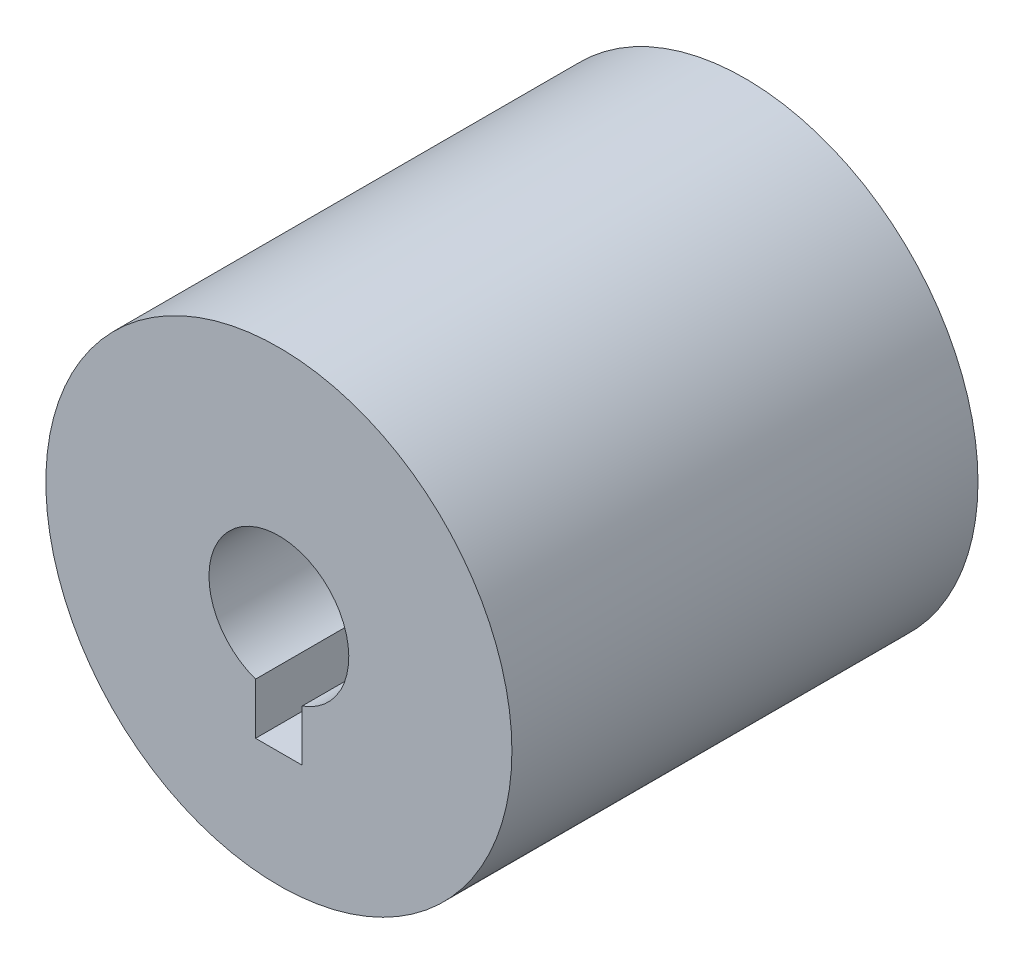
SolidWorks part; units mm, degrees
ref_plane "Front Plane" through (0, 0, 0) normal (0, 0, 1) x (1, 0, 0)
ref_plane "Top Plane" through (0, 0, 0) normal (0, 1, 0) x (1, 0, 0)
ref_plane "Right Plane" through (0, 0, 0) normal (1, 0, 0) x (0, 0, -1)
sketch "Sketch1" plane through (0, 0, 0) normal (0, 0, 1) x (1, 0, 0)
  circle A0 centre (0, 0) radius 5
  dimension "D1" = 10
extrude "Boss-Extrude1" add sketch "Sketch1" along normal blind 10
sketch "Sketch2" plane through (0, 0, 0) normal (0, 0, -1) x (-1, 0, 0)
  line L6 (-0.5, -1.4142) -> (-0.5, -2.5142)
  line L7 (-0.5, -2.5142) -> (0.5, -2.5142)
  line L8 (0.5, -1.4142) -> (0.5, -2.5142)
  arc A1 (0.5, -1.4142) -> (-0.5, -1.4142) centre (0, 0) ccw
  point P3 (0, -1.5)
  dimension "D1" = 3
  dimension "D2" = 1.1
  dimension "D3" = 1
extrude "Cut-Extrude1" cut sketch "Sketch2" against normal blind 10
sketch "Sketch3" plane through (0, 0, 10) normal (0, 0, 1) x (1, 0, 0)
  circle A1 centre (0, 0) radius 11
  dimension "D1" = 22
extrude "Boss-Extrude2" [suppressed] add sketch "Sketch3" along normal blind 6
sketch "Sketch4" [suppressed] plane through (0, 0, 16) normal (0, 0, 1) x (1, 0, 0)
  circle A0 centre (0, 0) radius 8 construction
  circle A1 centre (0, 8) radius 1
  circle A2 centre (6.9282, 4) radius 1
  circle A3 centre (6.9282, -4) radius 1
  circle A4 centre (0, -8) radius 1
  circle A5 centre (-6.9282, -4) radius 1
  circle A6 centre (-6.9282, 4) radius 1
  point P18 (0, 0)
  dimension "D1" = 16
  dimension "D2" = 2
  dimension "D3" = 6
extrude "Cut-Extrude2" [suppressed] cut sketch "Sketch4" against normal through all
sketch "Sketch5" [suppressed] plane through (0, 0, 16) normal (0, 0, 1) x (1, 0, 0)
  circle A0 centre (0, 0) radius 4
  dimension "D1" = 8
extrude "Cut-Extrude3" [suppressed] cut sketch "Sketch5" against normal blind 5.5
